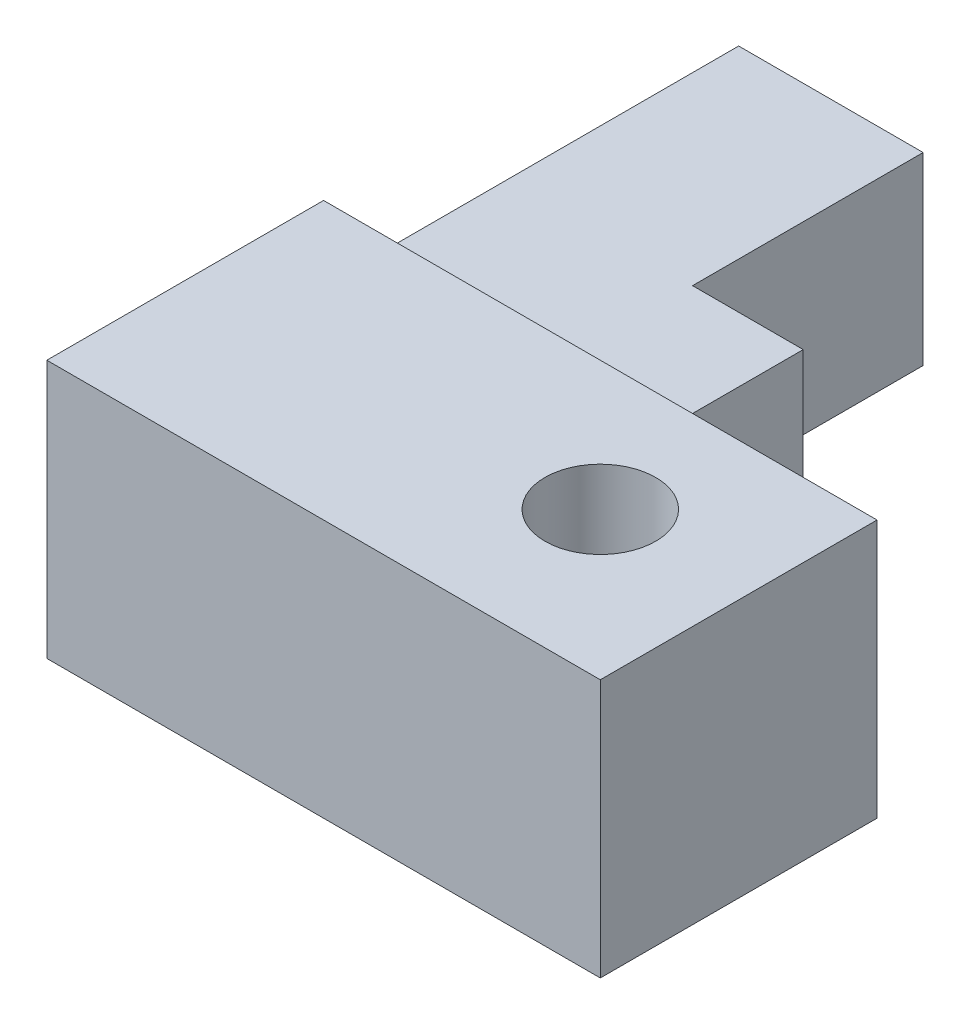
SolidWorks part; units mm, degrees
ref_plane "Front Plane" through (0, 0, 0) normal (0, 0, 1) x (1, 0, 0)
ref_plane "Top Plane" through (0, 0, 0) normal (0, 1, 0) x (1, 0, 0)
ref_plane "Right Plane" through (0, 0, 0) normal (1, 0, 0) x (0, 0, -1)
sketch "Sketch1" plane through (0, 0, 0) normal (0, 1, 0) x (1, 0, 0)
  line L0 (0, 0) -> (0, 75)
  line L1 (0, 75) -> (20, 75)
  line L2 (20, 75) -> (20, 50)
  line L3 (20, 50) -> (32, 50)
  line L4 (32, 50) -> (32, 38)
  line L5 (32, 38) -> (48, 38)
  line L6 (48, 38) -> (48, 30)
  line L7 (48, 30) -> (60, 30)
  line L8 (60, 30) -> (60, 0)
  line L9 (60, 0) -> (0, 0)
  line L10 (48, 30) -> (0, 30)
  circle A0 centre (44, 16) radius 6
  dimension "D9" = 12
  dimension "D10" = 16
  dimension "D11" = 16
  dimension "D1" = 75
  dimension "D2" = 30
  dimension "D3" = 60
  dimension "D4" = 20
  dimension "D5" = 12
  dimension "D6" = 20
  dimension "D7" = 12
  dimension "D8" = 12
extrude "Boss-Extrude1" add sketch "Sketch1" along normal blind 20 contours L10 L6 L5 L4 L3 L2 L1 L0 | L7 L10 L0 L9 L8 region at (29.0614, 0, -14.933) region at (16.0568, 0, -48.2666)
extrude "Boss-Extrude2" add sketch "Sketch1<3>" along normal blind 28 contours L7 L10 L0 L9 L8 region at (29.0614, 0, -14.933)
sketch "Sketch1<3>" plane through (0, 0, 0) normal (0, 1, 0) x (1, 0, 0) same geometry as "Sketch1"
